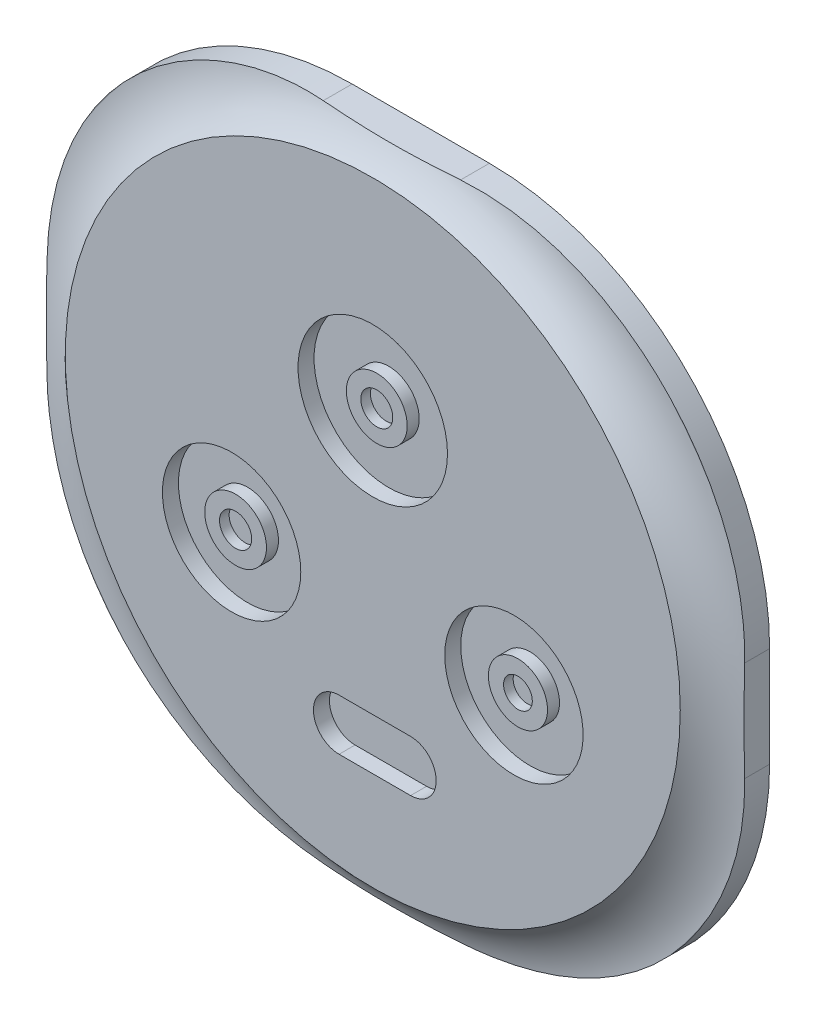
SolidWorks part; units mm, degrees
ref_plane "前视基准面" through (0, 0, 0) normal (0, 0, 1) x (1, 0, 0)
ref_plane "上视基准面" through (0, 0, 0) normal (0, 1, 0) x (1, 0, 0)
ref_plane "右视基准面" through (0, 0, 0) normal (1, 0, 0) x (0, 0, -1)
other "Configuration Table"
sketch "草图1" plane through (0, 0, 0) normal (0, 0, 1) x (1, 0, 0)
  line L1 (-15, 50) -> (2.1485, 50)
  line L2 (-50, 15) -> (-50, 2.4951)
  line L3 (-15, -32.5049) -> (2.1485, -32.5049)
  line L4 (37.1485, 15) -> (37.1485, 2.4951)
  line L5 (-50, 50) -> (37.1485, -32.5049) construction
  line L6 (-50, -32.5049) -> (37.1485, 50) construction
  arc A0 (-15, 50) -> (-50, 15) centre (-15, 15) ccw
  arc A1 (-15, -32.5049) -> (-50, 2.4951) centre (-15, 2.4951) cw
  arc A2 (2.1485, -32.5049) -> (37.1485, 2.4951) centre (2.1485, 2.4951) ccw
  arc A3 (37.1485, 15) -> (2.1485, 50) centre (2.1485, 15) ccw
  point P0 (-6.4257, 8.7475)
  dimension "D1" = 35
  dimension "D2" = 35
extrude "凸台-拉伸1" add sketch "草图1" along normal blind 3 contours A0 L2 A1 L3 A2 L4 A3 L1
sketch "草图2" plane through (0, 0, 3) normal (0, 0, 1) x (1, 0, 0)
  line L0 (-6.4257, 50) -> (-6.4257, -20.4556) construction
  line L2 (-50, 8.7475) -> (37.1485, 8.7475) construction
  circle A0 centre (-6.4257, 8.7475) radius 38.4111
  dimension "D1" = 76.8222
extrude "凸台-拉伸2" add sketch "草图2" along normal blind 3
fillet "圆角1" radius 10 1 edges at (31.9853, 8.7475, 3)
sketch "草图3" plane through (0, 0, 0) normal (0, 0, 1) x (1, 0, 0)
  line L0 (-6.4257, 47.1586) -> (-6.4257, -29.6636) construction
  line L1 (-44.8368, 8.7475) -> (31.9853, 8.7475) construction
sketch "草图4" plane through (0, 0, 6) normal (0, 0, 1) x (1, 0, 0)
  line L0 (-6.4257, 200047.1586) -> (-6.4257, -200029.6636) construction
  line L1 (-6.4257, 47.1586) -> (-6.4257, -29.6636) construction
  line L2 (-10.6362, -14.1227) -> (-1.702, -14.1227) construction
  line L3 (-10.6362, -10.9238) -> (-1.702, -10.9238)
  line L4 (-10.6362, -17.3216) -> (-1.702, -17.3216)
  circle A0 centre (-6.4257, 21.9541) radius 9.3345
  circle A1 centre (-24.0593, 0) radius 8.6408
  circle A4 centre (11.2078, 0) radius 8.6408
  arc A5 (-10.6362, -10.9238) -> (-10.6362, -17.3216) centre (-10.6362, -14.1227) ccw
  arc A6 (-1.702, -17.3216) -> (-1.702, -10.9238) centre (-1.702, -14.1227) ccw
  point P12 (-6.1691, -14.1227)
  dimension "D1" = 17.2815
  dimension "D2" = 18.6689
  dimension "D3" = 3.1989
  dimension "D4" = 8.9342
extrude "切除-拉伸1" cut sketch "草图4" against normal blind 2
sketch "草图5" plane through (0, 0, 4) normal (0, 0, 1) x (1, 0, 0)
  circle A0 centre (-6.4257, 21.9541) radius 3.8011
  circle A1 centre (-24.0593, 0) radius 3.8549
  circle A2 centre (11.2078, 0) radius 3.6929
  dimension "D1" = 7.7098
  dimension "D2" = 7.6022
extrude "凸台-拉伸3" add sketch "草图5" along normal blind 1.5
sketch "草图6" plane through (0, 0, 5.5) normal (0, 0, 1) x (1, 0, 0)
  circle A0 centre (-6.4257, 21.9541) radius 1.9964
  circle A1 centre (11.2078, 0) radius 1.7959
  circle A2 centre (-24.0593, 0) radius 2.007
  dimension "D1" = 4.014
extrude "切除-拉伸5" cut sketch "草图6" against normal blind 1.2
